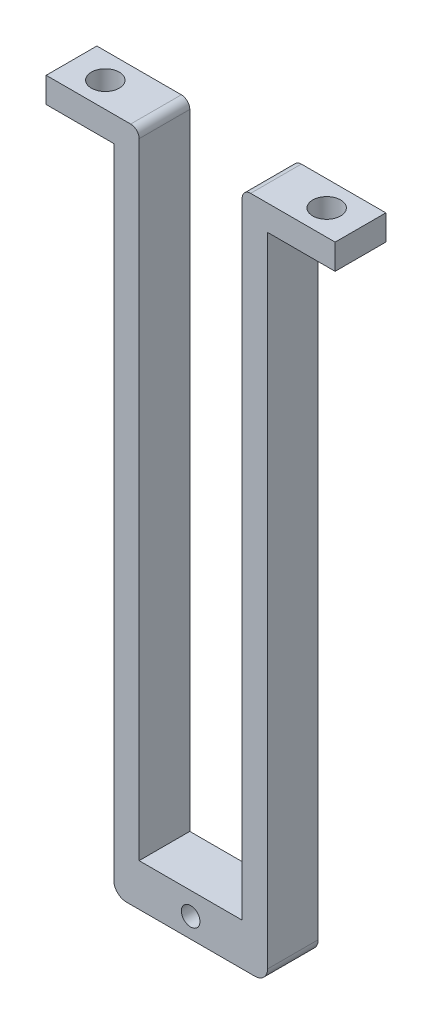
SolidWorks part; units mm, degrees
ref_plane "Front Plane" through (0, 0, 0) normal (0, 0, 1) x (1, 0, 0)
ref_plane "Top Plane" through (0, 0, 0) normal (0, 1, 0) x (1, 0, 0)
ref_plane "Right Plane" through (0, 0, 0) normal (1, 0, 0) x (0, 0, -1)
sketch "Sketch6" plane through (0, 0, 0) normal (0, 0, 1) x (1, 0, 0)
  line L0 (-6.1, 0) -> (6.1, 0)
  line L1 (6.1, 0) -> (6.1, 75)
  line L2 (6.1, 75) -> (17.1, 75)
  line L3 (17.1, 75) -> (17.1, 72)
  line L4 (17.1, 72) -> (9.1, 72)
  line L5 (9.1, 72) -> (9.1, -5)
  line L6 (9.1, -5) -> (-9.1, -5)
  line L7 (0, 4.2064) -> (0, -6.4903) construction
  line L8 (-9.1, 72) -> (-9.1, -5)
  line L9 (-17.1, 72) -> (-9.1, 72)
  line L10 (-17.1, 75) -> (-17.1, 72)
  line L11 (-6.1, 75) -> (-17.1, 75)
  line L12 (-6.1, 0) -> (-6.1, 75)
  point P12 (0, -5)
  point P17 (0, 0)
  dimension "D1" = 6.1
  dimension "D2" = 80
  dimension "D3" = 3
  dimension "D4" = 3
  dimension "D5" = 11
  dimension "D6" = 5
extrude "Boss-Extrude5" add sketch "Sketch6" along normal blind 6
sketch "Sketch7" plane through (0, 72, 0) normal (0, -1, 0) x (1, 0, 0)
  line L0 (-9.1, 6) -> (-9.1, 0) construction
  line L1 (9.1, 6) -> (9.1, 0) construction
  line L2 (-17.1, 6) -> (-9.1, 6) construction
  line L3 (9.1, 6) -> (17.1, 6) construction
  circle A0 centre (-13.1, 3) radius 1.65
  circle A1 centre (13.1, 3) radius 1.65
  dimension "D1" = 3.3
  dimension "D2" = 3.3
  dimension "D3" = 4
  dimension "D4" = 4
  dimension "D5" = 3
  dimension "D6" = 3
extrude "Cut-Extrude2" cut sketch "Sketch7" against normal up to surface (3 mm away) up to face at (-11.6, 75, 3)
fillet "Fillet1" radius 1 2 edges at (-6.1, 75, 3) (6.1, 75, 3)
fillet "Fillet2" radius 1.5 2 edges at (9.1, -5, 3) (-9.1, -5, 3)
sketch "Sketch8" plane through (0, 0, 6) normal (0, 0, 1) x (1, 0, 0)
  circle A1 centre (0, -2.65) radius 1.1
extrude "Cut-Extrude3" cut sketch "Sketch8" against normal up to surface (6 mm away) up to face at (0, 44.9246, 0)
equation "\"D2@Sketch7\"=\"D1@Sketch7\""
equation "\"D4@Sketch7\"=\"D3@Sketch7\""
